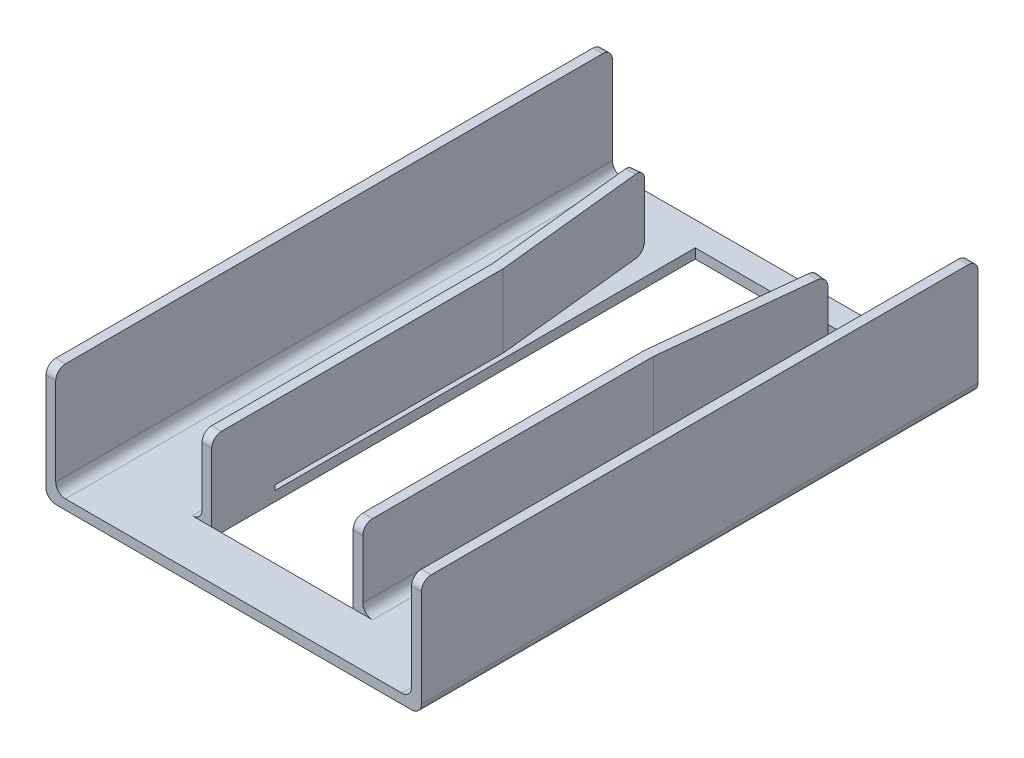
SolidWorks part; units mm, degrees
ref_plane "Front Plane" through (0, 0, 0) normal (0, 0, 1) x (1, 0, 0)
ref_plane "Top Plane" through (0, 0, 0) normal (0, 1, 0) x (1, 0, 0)
ref_plane "Right Plane" through (0, 0, 0) normal (1, 0, 0) x (0, 0, -1)
sketch "Sketch2" plane through (0, 0, 0) normal (0, 0, 1) x (1, 0, 0)
  line L1 (-1.25, 0) -> (1.25, 0) construction
  line L2 (1.925, -0.6) -> (1.925, 0.6) construction
  line L3 (-1.925, -0.6) -> (1.925, -0.6) construction
  line L4 (-1.925, 0.6) -> (-1.925, -0.6) construction
  line L5 (1.925, -0.6) -> (1.925, 0.6)
  line L6 (-1.925, -0.6) -> (1.925, -0.6)
  line L7 (-1.925, 0.6) -> (-1.925, -0.6)
  line L8 (-1.825, 0.6) -> (-1.825, -0.5)
  line L9 (-1.825, -0.5) -> (1.825, -0.5)
  line L10 (1.825, -0.5) -> (1.825, 0.6)
  line L11 (-1.925, 0.6) -> (-1.825, 0.6)
  line L12 (1.925, 0.6) -> (1.825, 0.6)
  point P0 (0, 0)
  dimension "D1" = 0.1
  dimension "pinSpacing" = 2.5
extrude "Boss-Extrude1" add sketch "Sketch2" against normal up to surface (5.71 mm away)
sketch "Sketch3" plane through (0, -0.5, 0) normal (0, 1, 0) x (1, 0, 0)
  line L0 (-1.825, 5.71) -> (-1.825, 0) construction
  line L1 (0.725, 0.5) -> (-0.725, 0.5)
  line L2 (0.725, 0.5) -> (0.725, 5.46)
  line L3 (0.725, 5.46) -> (-0.725, 5.46)
  line L4 (-0.725, 0.5) -> (-0.725, 5.46)
  line L5 (0.725, 0.5) -> (-0.725, 5.46) construction
  line L6 (0.725, 5.46) -> (-0.725, 0.5) construction
  line L7 (-1.825, 0) -> (1.825, 0) construction
  point P0 (0, 2.98)
  dimension "D1" = 1.1
  dimension "D2" = 0.5
extrude "Cut-Extrude1" cut sketch "Sketch3" against normal through all
sketch "Sketch4" plane through (0, -0.5, 0) normal (0, 1, 0) x (1, 0, 0)
  line L0 (0, 0) -> (0, 5.71) construction
  line L1 (-1.825, 5.71) -> (1.825, 5.71) construction
  line L2 (-0.725, 5.46) -> (-0.725, 0.5) construction
  line L3 (-0.725, 3.4871) -> (-0.725, 0.5)
  line L4 (-0.725, 0.5) -> (-0.825, 0.5)
  line L5 (-0.825, 0.5) -> (-0.825, 3.4818)
  line L6 (-0.825, 3.4818) -> (-0.995, 5.0995)
  line L7 (-0.995, 5.0995) -> (-0.8956, 5.11)
  line L8 (-0.8956, 5.11) -> (-0.725, 3.4871)
  line L9 (-0.725, 1.1475) -> (-0.825, 1.1475)
  line L10 (0.725, 0.5) -> (0.825, 0.5)
  line L11 (0.725, 1.1475) -> (0.825, 1.1475)
  line L12 (0.725, 3.4871) -> (0.725, 0.5)
  line L13 (0.825, 0.5) -> (0.825, 3.4818)
  line L14 (0.825, 3.4818) -> (0.995, 5.0995)
  line L15 (0.995, 5.0995) -> (0.8956, 5.11)
  line L16 (0.8956, 5.11) -> (0.725, 3.4871)
  line M9 (-0.725, 0.5) -> (-0.725, 5.46)
  line M11 (0.725, 5.46) -> (0.725, 0.5)
  dimension "D1" = 0.1
  dimension "D2" = 6
  dimension "D3" = 6
  dimension "D4" = 0.1
  dimension "D5" = 0.6
extrude "Boss-Extrude2" add sketch "Sketch4" along normal blind 0.05 contours L9 L5 L4 M9 | L10 L13 L11 M11 region at (-0.775, -0.5, -0.8238) region at (0.775, -0.5, -0.8238)
extrude "Boss-Extrude3" add sketch "Sketch4<3>" along normal blind 0.75 from surface contours L9 L5 L4 M9 | L9 L3 L8 L7 L6 L5 | L10 L13 L11 M11 | L15 L16 L11 L13 L14 M11 region at (-0.81, -0.5, -3.1288) region at (-0.775, -0.5, -0.8238) region at (0.775, -0.5, -0.8238) region at (0.81, -0.5, -3.1288) starting at face at (-0.775, -0.45, -0.8238)
sketch "Sketch4<3>" plane through (0, -0.5, 0) normal (0, 1, 0) x (1, 0, 0) same geometry as "Sketch4"
fillet "Fillet1" radius 0.1 16 edges at (-1.875, 0.6, -5.71) (1.875, 0.6, -5.71) (0.9453, -0.45, -5.1048) (0.9453, 0.3, -5.1048) (-0.9453, -0.45, -5.1048) (-0.9453, 0.3, -5.1048) (-0.775, 0.3, -0.5) (0.775, 0.3, -0.5) (1.875, 0.6, 0) (-1.875, 0.6, 0) (-0.825, -0.5, -0.8238) (0.825, -0.5, -0.8238) (1.825, -0.5, -2.855) (-1.825, -0.5, -2.855) (1.925, -0.6, -2.855) (-1.925, -0.6, -2.855)
